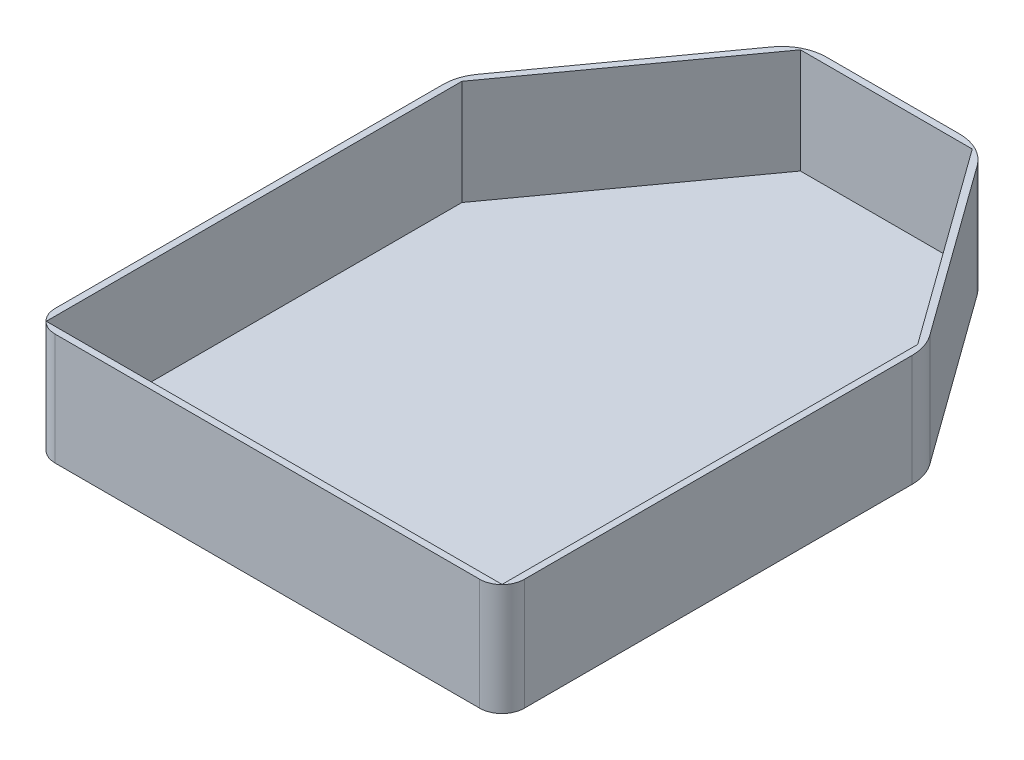
SolidWorks part; units mm, degrees
ref_plane "Front Plane" through (0, 0, 0) normal (0, 0, 1) x (1, 0, 0)
ref_plane "Top Plane" through (0, 0, 0) normal (0, 1, 0) x (1, 0, 0)
ref_plane "Right Plane" through (0, 0, 0) normal (1, 0, 0) x (0, 0, -1)
sketch "Sketch1" plane through (0, 0, 0) normal (0, 1, 0) x (1, 0, 0)
  line L0 (0, 280) -> (0, 0) construction
  line L1 (-40, 280) -> (40, 280)
  line L2 (-105, 190) -> (-105, 0)
  line L3 (-105, 0) -> (105, 0)
  line L4 (105, 190) -> (105, 0)
  line L5 (-40, 280) -> (-105, 190)
  line L6 (40, 280) -> (105, 190)
  line L8 (-25, 140) -> (25, 140)
  line L9 (-25, 140) -> (-25, 0)
  line L10 (-25, 0) -> (25, 0)
  line L11 (25, 140) -> (25, 0)
  point P4 (0, 0)
  point P14 (0, 0)
  dimension "D1" = 280
  dimension "D2" = 210
  dimension "D3" = 80
  dimension "D4" = 90
  dimension "D5" = 140
  dimension "D6" = 50
extrude "Boss-Extrude1" add sketch "Sketch1" along normal blind 50 contours L2 L3 L4 L6 L1 L5
shell "Shell1" thickness 3 removed face at (0, 50, -156.6667)
fillet "Fillet3" radius 10 2 edges at (-105, 25, 0) (105, 25, 0)
fillet "Fillet6" radius 20 4 edges at (105, 25, -190) (40, 25, -280) (-40, 25, -280) (-105, 25, -190)
sketch "Sketch3" plane through (0, 0, 0) normal (0, 0, 1) x (1, 0, 0)
  line L0 (-25, 0) -> (25, 0) construction
  line L1 (-25, 0) -> (25, 0)
  line L2 (-25, 0) -> (-25, 25)
  line L3 (-25, 25) -> (25, 25)
  line L4 (25, 0) -> (25, 25)
  line L5 (-40, 0) -> (40, 0) construction
  point P4 (24.9562, 0)
  point P7 (-25, 0)
  dimension "D1" = 25
